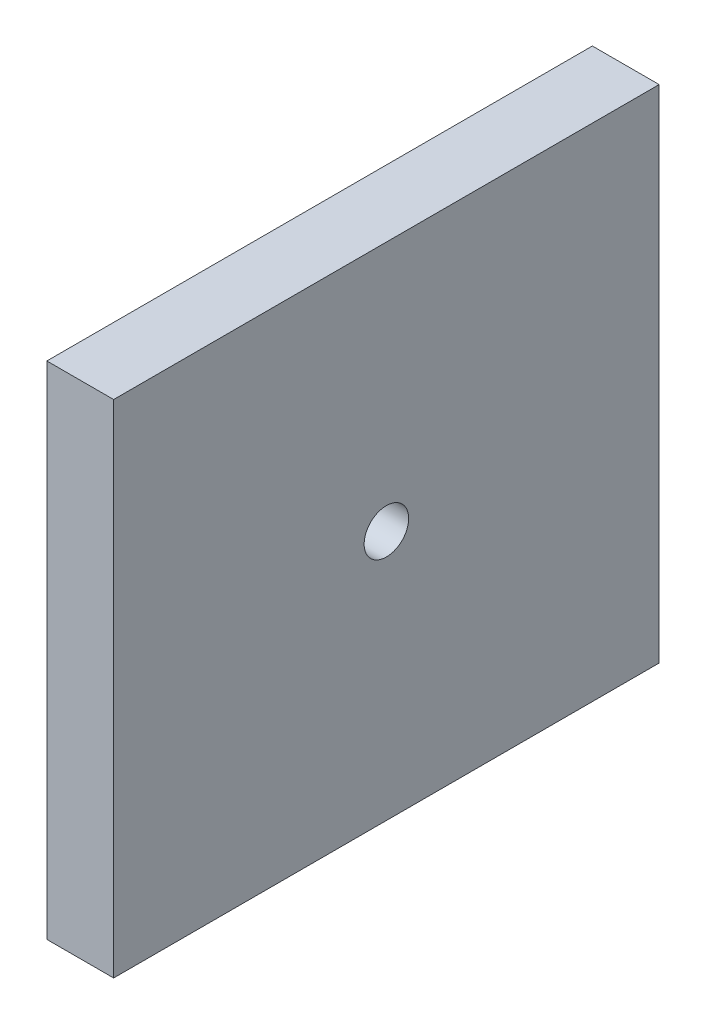
SolidWorks part; units mm, degrees
ref_plane "Ebene vorne" through (0, 0, 0) normal (0, 0, 1) x (1, 0, 0)
ref_plane "Ebene oben" through (0, 0, 0) normal (0, 1, 0) x (1, 0, 0)
ref_plane "Ebene rechts" through (0, 0, 0) normal (1, 0, 0) x (0, 0, -1)
sketch "Sketch1" plane through (0, 0, 0) normal (1, 0, 0) x (0, 0, -1)
  line L0 (0, 39.4227) -> (0, -41.65) construction
  line L1 (-49, 45) -> (49, 45)
  line L2 (-49, 45) -> (-49, -45)
  line L3 (-49, -45) -> (49, -45)
  line L4 (49, 45) -> (49, -45)
  line L5 (48.1091, 0) -> (-28.5091, 0) construction
  dimension "D1" = 98
  dimension "D2" = 90
extrude "Boss-Extrude1" add sketch "Sketch1" along normal blind 12
sketch "Sketch2" plane through (12, 0, 0) normal (1, 0, 0) x (0, 0, -1)
  circle A0 centre (0, 0) radius 4
  dimension "D1" = 8
extrude "Cut-Extrude1" cut sketch "Sketch2" against normal through all
